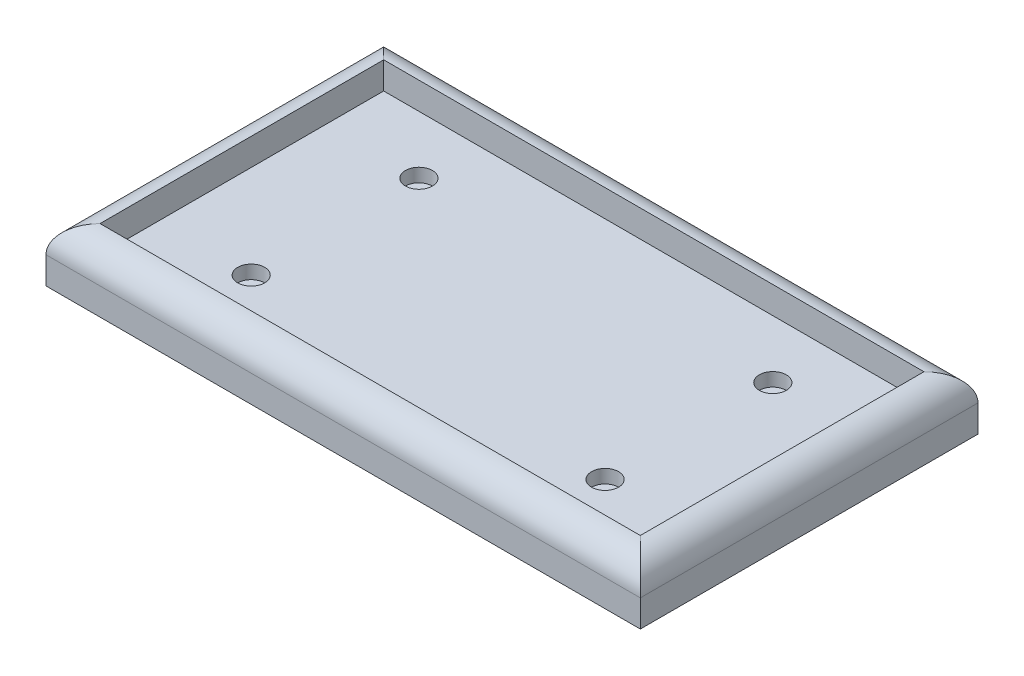
SolidWorks part; units mm, degrees
ref_plane "Front Plane" through (0, 0, 0) normal (0, 0, 1) x (1, 0, 0)
ref_plane "Top Plane" through (0, 0, 0) normal (0, 1, 0) x (1, 0, 0)
ref_plane "Right Plane" through (0, 0, 0) normal (1, 0, 0) x (0, 0, -1)
sketch "Sketch1" plane through (0, 0, 0) normal (0, 1, 0) x (1, 0, 0)
  line L1 (110, 62.5) -> (-110, 62.5)
  line L2 (110, 62.5) -> (110, -62.5)
  line L3 (110, -62.5) -> (-110, -62.5)
  line L4 (-110, 62.5) -> (-110, -62.5)
  line L5 (110, 62.5) -> (-110, -62.5) construction
  line L6 (110, -62.5) -> (-110, 62.5) construction
  point P0 (0, 0)
extrude "Boss-Extrude1" add sketch "Sketch1" along normal blind 20
sketch "Sketch2" plane through (0, 20, 0) normal (0, 1, 0) x (1, 0, 0)
  line L1 (100, 52.5) -> (-100, 52.5)
  line L2 (100, 52.5) -> (100, -52.5)
  line L3 (100, -52.5) -> (-100, -52.5)
  line L4 (-100, 52.5) -> (-100, -52.5)
  line L5 (100, 52.5) -> (-100, -52.5) construction
  line L6 (100, -52.5) -> (-100, 52.5) construction
  point P0 (0, 0)
extrude "Cut-Extrude1" cut sketch "Sketch2" against normal blind 10
fillet "Fillet1" radius 10 4 edges at (110, 20, 0) (0, 20, 62.5) (0, 20, -62.5) (-110, 20, 0)
sketch "Sketch3" plane through (0, 0, 0) normal (0, -1, 0) x (1, 0, 0)
  line L1 (85.5, 51.045) -> (-85.5, 51.045)
  line L2 (85.5, 51.045) -> (85.5, -51.045)
  line L3 (85.5, -51.045) -> (-85.5, -51.045)
  line L4 (-85.5, 51.045) -> (-85.5, -51.045)
  line L5 (85.5, 51.045) -> (-85.5, -51.045) construction
  line L6 (85.5, -51.045) -> (-85.5, 51.045) construction
  point P0 (0, 0)
extrude "Boss-Extrude2" add sketch "Sketch3" along normal blind 5
sketch "Sketch4" plane through (0, -5, 0) normal (0, -1, 0) x (1, 0, 0)
  circle A0 centre (-65.5, 31.045) radius 2
  circle A1 centre (-65.5, -31.045) radius 2
  circle A2 centre (65.5, -31.045) radius 2
  circle A3 centre (65.5, 31.045) radius 2
extrude "Cut-Extrude2" cut sketch "Sketch4" against normal through all
sketch "Sketch5" plane through (0, 10, 0) normal (0, 1, 0) x (1, 0, 0)
  circle A0 centre (-65.5, 31.045) radius 5
  circle A1 centre (-65.5, -31.045) radius 5
  circle A2 centre (65.5, -31.045) radius 5
  circle A3 centre (65.5, 31.045) radius 5
extrude "Cut-Extrude3" cut sketch "Sketch5" against normal blind 5
